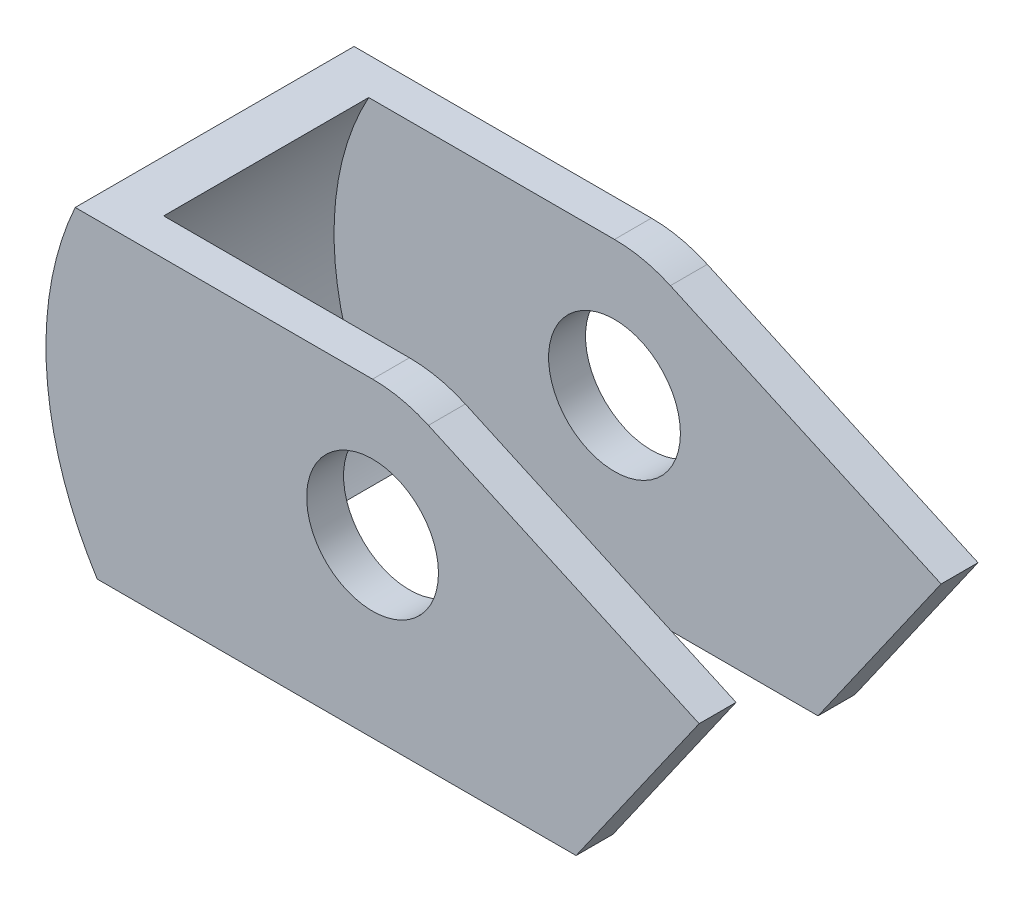
SolidWorks part; units mm, degrees
ref_plane "Front Plane" through (0, 0, 0) normal (0, 0, 1) x (1, 0, 0)
ref_plane "Top Plane" through (0, 0, 0) normal (0, 1, 0) x (1, 0, 0)
ref_plane "Right Plane" through (0, 0, 0) normal (1, 0, 0) x (0, 0, -1)
sketch "Sketch1" plane through (0, 0, 0) normal (0, 0, 1) x (1, 0, 0)
  line L0 (0, 0) -> (0, -38.1) construction
  line L1 (70.8, 0) -> (44.1221, -38.1)
  line L2 (70.8, 0) -> (12.1152, 26.6642)
  line L4 (0, 0) -> (0, -38.1)
  line L7 (0, -38.1) -> (-59.6744, -38.1)
  line L8 (0, -38.1) -> (56.8919, -38.1)
  line L9 (0, 29.2875) -> (-64.4584, 29.2875)
  circle A0 centre (0, 0) radius 14.2875
  circle A1 centre (0, 0) radius 29.2875
  arc A5 (-70.8, 0) -> (-59.6744, -38.1) centre (0, 0) ccw
  arc A6 (-60.6239, 4.6236) -> (-47.3817, -38.1) centre (0, 0) ccw
  arc A8 (-64.4584, 29.2875) -> (-59.6744, -38.1) centre (0, 0) ccw
  arc A9 (-53.2812, 29.2875) -> (-47.3817, -38.1) centre (0, 0) ccw
  dimension "D1" = 28.575
  dimension "D3" = 38.1
  dimension "D2" = 15
extrude "Boss-Extrude1" add sketch "Sketch1" along normal blind 8 contours A1 L0 L1 L2 | L0 A1 A6 | A0 A1 | A6 A5 region at (-28.4591, 0, 0) region at (37.6484, -13.5239, 0) region at (-37.5172, -5.9462, 0) region at (-62.437, -4.8952, 0)
extrude "Boss-Extrude2" add sketch "Sketch1<3>" against normal blind 44.45 contours A6 A5 region at (-62.437, -4.8952, 0)
sketch "Sketch1<3>" plane through (0, 0, 0) normal (0, 0, 1) x (1, 0, 0) same geometry as "Sketch1"
ref_plane "Plane1" through (0, 0, -22.225) normal (0, 0, -1) x (-1, 0, 0)
mirror "Mirror1" about plane through (0, 0, -22.225) normal (0, 0, -1) of "Boss-Extrude1"
